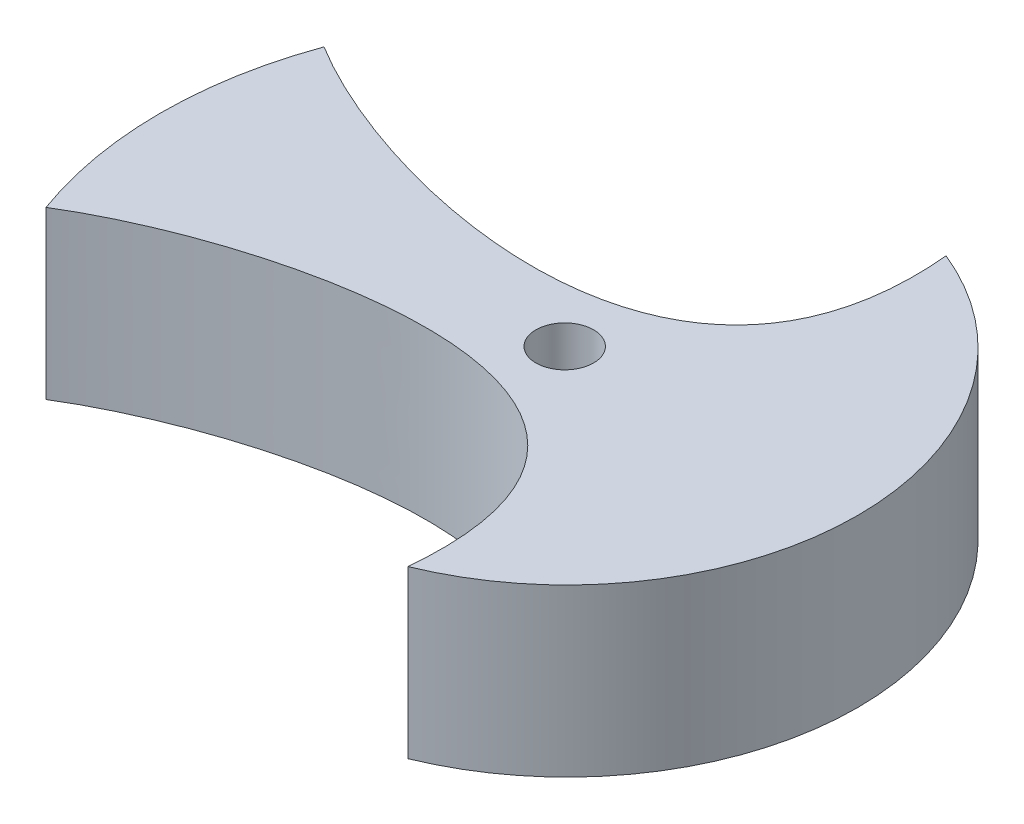
SolidWorks part; units mm, degrees
material "PLA"
ref_plane "Front Plane" through (0, 0, 0) normal (0, 0, 1) x (1, 0, 0)
ref_plane "Top Plane" through (0, 0, 0) normal (0, 1, 0) x (1, 0, 0)
ref_plane "Right Plane" through (0, 0, 0) normal (1, 0, 0) x (0, 0, -1)
other "Center of Mass"
sketch "Sketch2" plane through (0, 0, 0) normal (0, 1, 0) x (1, 0, 0)
  line L0 (0, 0) -> (-63.5, 0)
  line L1 (0, 0) -> (63.5, 0)
  circle A0 centre (0, 0) radius 63.5 construction
  arc A2 (-59.6705, -21.7183) -> (-59.6705, 21.7183) centre (0, 0) cw
  arc A3 (17.1974, -42.0478) -> (17.1974, 42.0478) centre (0, 0) ccw
  spline S0 degree 3 poles (-59.6705, 21.7183) (-35.8281, 6.9894) (21.7167, -5.9231) (17.1974, 42.0478) knots 0 0 0 0 1 1 1 1
  spline S1 degree 3 poles (-59.6705, -21.7183) (-35.8281, -6.9894) (21.7167, 5.9231) (17.1974, -42.0478) knots 0 0 0 0 1 1 1 1
  point P6 (13.8894, 51.2291)
  point P9 (13.8079, 46.2845)
  point P11 (27.5798, 32.5784)
  point P12 (15.5606, 39.7477)
  point P17 (15.839, 41.8327)
  point P18 (16.6751, 42.9899)
  point P19 (17.1974, 42.0478)
  dimension "D1" = 127
  dimension "D2" = 160
extrude "Boss-Extrude1" add sketch "Sketch2" along normal blind 26 contours A2 L0 | S0 A2 L0 region at (22.7144, 0, 1.1676) region at (-31.75, 0, -1.1676)
other "Center of Mass Reference Point1"
sketch "Sketch3" plane through (0, 0, 0) normal (0, -1, 0) x (1, 0, 0)
  circle A0 centre (-0.3382, 0.0001) radius 4.5
  point P0 (0, 0)
  point P4 (-0.3382, 0.0001)
  point P6 (0, 0)
  dimension "D1" = 9
extrude "Cut-Extrude1" cut sketch "Sketch3" against normal through all
